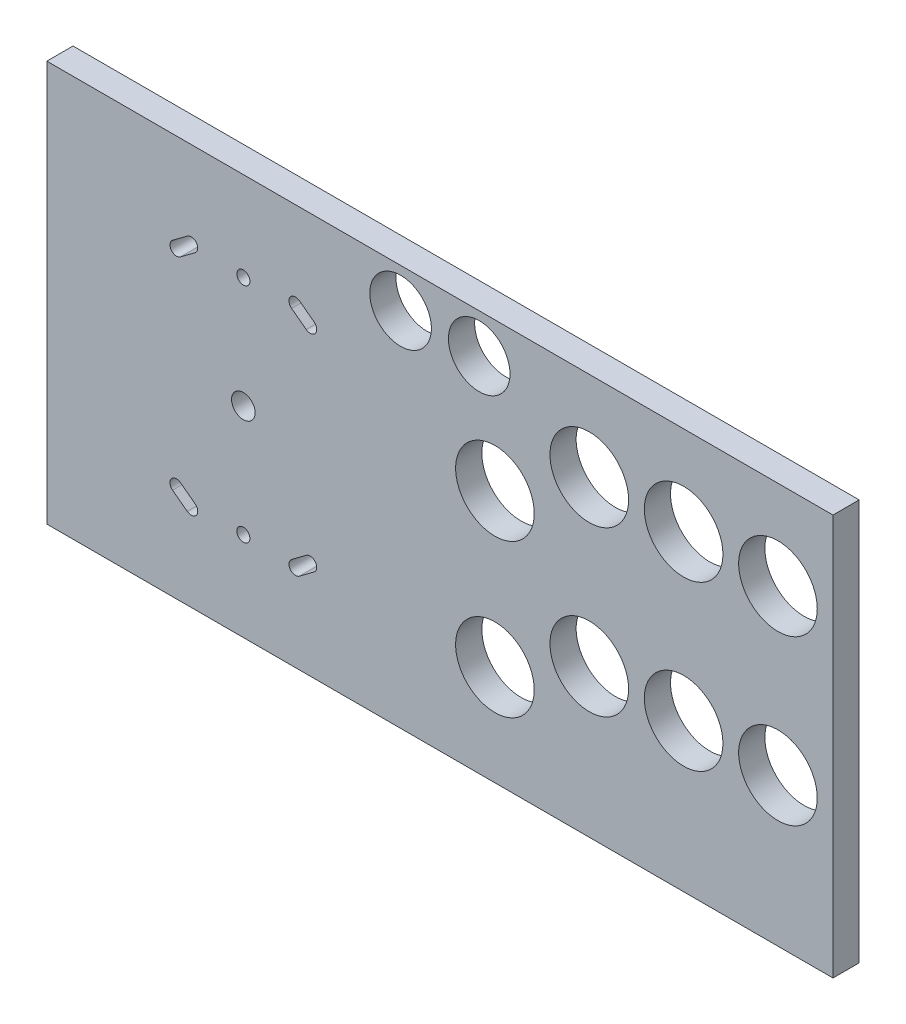
SolidWorks part; units mm, degrees
ref_plane "Plan de face" through (0, 0, 0) normal (0, 0, 1) x (1, 0, 0)
ref_plane "Plan de dessus" through (0, 0, 0) normal (0, 1, 0) x (1, 0, 0)
ref_plane "Plan de droite" through (0, 0, 0) normal (1, 0, 0) x (0, 0, -1)
sketch "Esquisse1" plane through (0, 0, 0) normal (0, 0, 1) x (1, 0, 0)
  line L0 (0, 76.5) -> (300, 76.5) construction
  line L1 (0, 0) -> (300, 0)
  line L2 (0, 0) -> (0, 153)
  line L3 (0, 153) -> (300, 153)
  line L4 (300, 0) -> (300, 153)
  line L5 (150, 153) -> (150, 0) construction
  dimension "D1" = 300
  dimension "D2" = 153
extrude "Boss.-Extru.1" add sketch "Esquisse1" along normal blind 10
sketch "Esquisse2" plane through (0, 0, 10) normal (0, 0, 1) x (1, 0, 0)
  line L0 (150, 153) -> (150, 0) construction
  line L1 (300, 153) -> (0, 153) construction
  line L2 (0, 0) -> (300, 0) construction
  line L3 (150, 0) -> (150, 76.5) construction
  line L4 (150, 76.5) -> (300, 76.5) construction
  line L5 (300, 0) -> (300, 153) construction
  line L6 (0, 153) -> (0, 0) construction
  line L7 (45, 124) -> (105, 124)
  line L8 (45, 124) -> (45, 29)
  line L9 (45, 29) -> (105, 29)
  line L10 (105, 124) -> (105, 29)
  dimension "D1" = 60
  dimension "D2" = 95
  dimension "D3" = 29
  dimension "D4" = 45
sketch "Esquisse3" plane through (0, 0, 10) normal (0, 0, 1) x (1, 0, 0)
  line L0 (75, 124) -> (75, 29) construction
  line L1 (45, 124) -> (105, 124) construction
  line L2 (45, 29) -> (105, 29) construction
  line L3 (45, 76.5) -> (105, 76.5) construction
  line L4 (45, 124) -> (45, 29) construction
  line L5 (105, 124) -> (105, 29) construction
  line L6 (93.4, 118) -> (99, 113.8)
  line L8 (102, 117.8) -> (96.4, 122)
  line L9 (48, 117.8) -> (53.6, 122)
  line L10 (56.6, 118) -> (51, 113.8)
  line L11 (48, 35.2) -> (53.6, 31)
  line L12 (56.6, 35) -> (51, 39.2)
  line L13 (102, 35.2) -> (96.4, 31)
  line L14 (93.4, 35) -> (99, 39.2)
  arc A0 (96.4, 122) -> (93.4, 118) centre (94.9, 120) ccw
  arc A1 (99, 113.8) -> (102, 117.8) centre (100.5, 115.8) ccw
  arc A2 (53.6, 122) -> (56.6, 118) centre (55.1, 120) cw
  arc A3 (51, 113.8) -> (48, 117.8) centre (49.5, 115.8) cw
  arc A4 (51, 39.2) -> (48, 35.2) centre (49.5, 37.2) ccw
  arc A5 (53.6, 31) -> (56.6, 35) centre (55.1, 33) ccw
  arc A6 (96.4, 31) -> (93.4, 35) centre (94.9, 33) cw
  arc A7 (99, 39.2) -> (102, 35.2) centre (100.5, 37.2) cw
  dimension "D1" = 7
  dimension "D2" = 5
  dimension "D3" = 3
  dimension "D4" = 2
  dimension "D5" = 6
  dimension "D6" = 2.5
extrude "Enlèv. mat.-Extru.2" cut sketch "Esquisse3" against normal through all contours L6 A1 L8 A0 | L10 A3 L9 A2 | L11 A5 L12 A4 | L14 A7 L13 A6
sketch "Esquisse5" plane through (0, 0, 10) normal (0, 0, 1) x (1, 0, 0)
  line L0 (75, 124) -> (75, 29) construction
  line L1 (45, 124) -> (105, 124) construction
  line L2 (45, 29) -> (105, 29) construction
  line L3 (45, 76.5) -> (105, 76.5) construction
  line L4 (45, 124) -> (45, 29) construction
  line L5 (105, 124) -> (105, 29) construction
  circle A0 centre (75, 76.5) radius 4.5
  circle A1 centre (75, 119) radius 2.5
  circle A2 centre (75, 34) radius 2.5
  dimension "D1" = 5
  dimension "D2" = 5
  dimension "D5" = 9
  dimension "D3" = 5
  dimension "D4" = 5
extrude "Enlèv. mat.-Extru.3" cut sketch "Esquisse5" against normal through all contours A1 | A0 | A2
sketch "Esquisse6" plane through (0, 0, 10) normal (0, 0, 1) x (1, 0, 0)
  line L0 (300, 153) -> (0, 153) construction
  line L1 (150, 153) -> (150, 0) construction
  line L2 (150, 153) -> (150, 0) construction
  circle A0 centre (165, 138) radius 11.75
  circle A1 centre (135, 138) radius 11.75
  dimension "D1" = 23.5
  dimension "D2" = 15
  dimension "D3" = 15
extrude "Enlèv. mat.-Extru.4" cut sketch "Esquisse6" against normal through all contours A0 | A1
sketch "Esquisse7" plane through (0, 0, 10) normal (0, 0, 1) x (1, 0, 0)
  line L0 (150, 76.5) -> (300, 76.5) construction
  line L1 (150, 153) -> (150, 0) construction
  circle A0 centre (171, 96.5) radius 15
  point P4 (0, 0)
  point P6 (154.1027, 111.1448)
  dimension "D1" = 30
  dimension "D2" = 20
  dimension "D3" = 21
extrude "Enlèv. mat.-Extru.5" cut sketch "Esquisse7" against normal through all contours A0
sketch "Esquisse8" plane through (0, 0, 10) normal (0, 0, 1) x (1, 0, 0)
  line L0 (150, 76.5) -> (300, 76.5) construction
  circle A0 centre (207, 119) radius 15
  circle A1 centre (171, 96.5) radius 15 construction
  dimension "D1" = 30
  dimension "D2" = 36
  dimension "D3" = 42.5
extrude "Enlèv. mat.-Extru.6" cut sketch "Esquisse8" against normal through all
sketch "Esquisse9" plane through (0, 0, 10) normal (0, 0, 1) x (1, 0, 0)
  line L0 (150, 76.5) -> (300, 76.5) construction
  circle A0 centre (243, 119) radius 15
  circle A1 centre (207, 119) radius 15 construction
  dimension "D1" = 30
  dimension "D2" = 36
  dimension "D3" = 42.5
extrude "Enlèv. mat.-Extru.7" cut sketch "Esquisse9" against normal through all
sketch "Esquisse10" plane through (0, 0, 10) normal (0, 0, 1) x (1, 0, 0)
  line L0 (150, 76.5) -> (300, 76.5) construction
  circle A0 centre (279, 119) radius 15
  circle A1 centre (243, 119) radius 15 construction
  dimension "D1" = 30
  dimension "D2" = 36
  dimension "D3" = 42.5
extrude "Enlèv. mat.-Extru.8" cut sketch "Esquisse10" against normal through all
sketch "Esquisse11" plane through (0, 0, 10) normal (0, 0, 1) x (1, 0, 0)
  line L0 (150, 76.5) -> (300, 76.5) construction
  line L1 (150, 153) -> (150, 0) construction
  circle A0 centre (171, 38.2) radius 15
  dimension "D1" = 30
  dimension "D2" = 38.3
  dimension "D3" = 21
extrude "Enlèv. mat.-Extru.9" cut sketch "Esquisse11" against normal through all
sketch "Esquisse12" plane through (0, 0, 10) normal (0, 0, 1) x (1, 0, 0)
  line L0 (150, 76.5) -> (300, 76.5) construction
  circle A0 centre (207, 56.5) radius 15
  circle A1 centre (171, 38.2) radius 15 construction
  dimension "D1" = 30
  dimension "D2" = 20
  dimension "D3" = 36
extrude "Enlèv. mat.-Extru.10" cut sketch "Esquisse12" against normal through all
sketch "Esquisse13" plane through (0, 0, 10) normal (0, 0, 1) x (1, 0, 0)
  line L0 (150, 76.5) -> (300, 76.5) construction
  circle A0 centre (243, 56.5) radius 15
  circle A1 centre (207, 56.5) radius 15 construction
  dimension "D1" = 30
  dimension "D2" = 20
  dimension "D3" = 36
extrude "Enlèv. mat.-Extru.11" cut sketch "Esquisse13" against normal through all
sketch "Esquisse14" plane through (0, 0, 10) normal (0, 0, 1) x (1, 0, 0)
  line L0 (150, 76.5) -> (300, 76.5) construction
  circle A0 centre (279, 56.5) radius 15
  circle A1 centre (243, 56.5) radius 15 construction
  dimension "D1" = 30
  dimension "D2" = 20
  dimension "D3" = 36
extrude "Enlèv. mat.-Extru.12" cut sketch "Esquisse14" against normal through all
